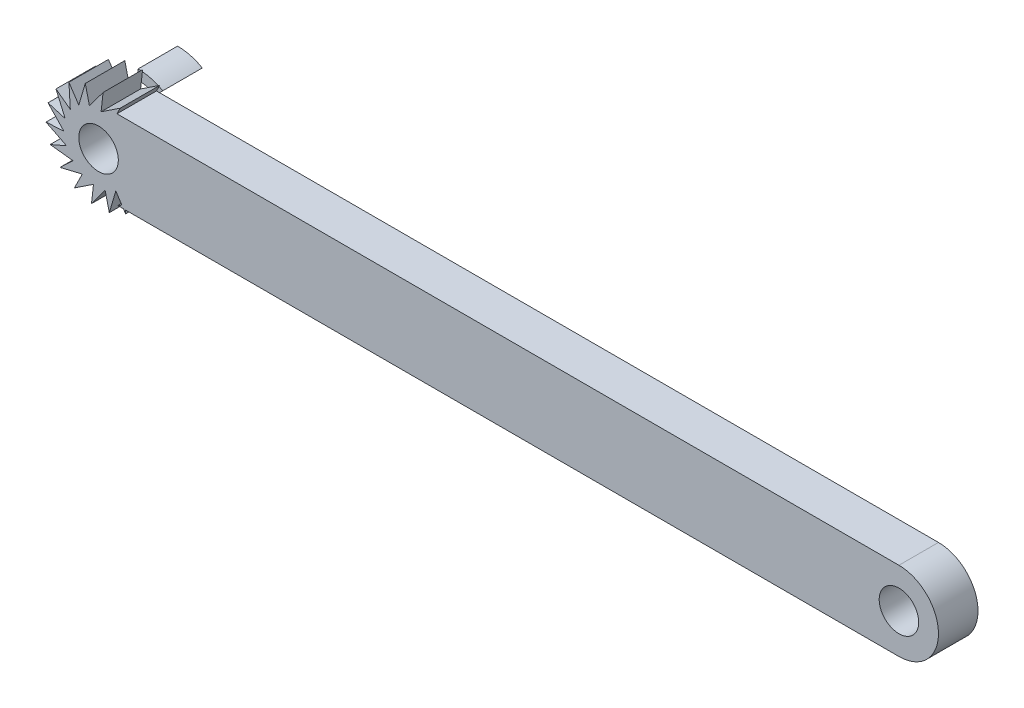
SolidWorks part; units mm, degrees
material "1060 Alloy"
ref_plane "Front Plane" through (0, 0, 0) normal (0, 0, 1) x (1, 0, 0)
ref_plane "Top Plane" through (0, 0, 0) normal (0, 1, 0) x (1, 0, 0)
ref_plane "Right Plane" through (0, 0, 0) normal (1, 0, 0) x (0, 0, -1)
sketch "Sketch1" plane through (0, 0, 0) normal (0, 0, 1) x (1, 0, 0)
  line L0 (-71.3706, 0) -> (333.6294, 0) construction
  line L1 (-71.3706, 20) -> (333.6294, 20)
  line L2 (-71.3706, -20) -> (333.6294, -20)
  arc A0 (-71.3706, 20) -> (-71.3706, -20) centre (-71.3706, 0) ccw
  arc A1 (333.6294, -20) -> (333.6294, 20) centre (333.6294, 0) ccw
  circle A2 centre (-71.3706, 0) radius 10
  circle A3 centre (333.6294, 0) radius 10
  point P3 (131.1294, 0)
extrude "Boss-Extrude1" add sketch "Sketch1" along normal blind 20
sketch "Sketch2" plane through (0, 0, 0) normal (0, 0, -1) x (-1, 0, 0)
  line L0 (71.3706, -20) -> (71.3706, -25)
  line L1 (62.5643, -17.9569) -> (58.8706, -21.6506)
  arc A0 (62.5643, -17.9569) -> (71.3706, -20) centre (71.3706, 0) ccw
  arc A1 (58.8706, -21.6506) -> (71.3706, -25) centre (71.3706, 0) ccw
  arc A2 (71.3706, -20) -> (71.3706, 20) centre (71.3706, 0) ccw construction
  dimension "D1" = 50
  dimension "D2" = 45
extrude "Boss-Extrude2" add sketch "Sketch2" along normal blind 20
ref_plane "Plane1" through (0, 0, 15) normal (0, 0, 1) x (1, 0, 0)
sketch "Sketch5" plane through (0, 0, 15) normal (0, 0, 1) x (1, 0, 0)
  circle A0 centre (-72.0022, 0) radius 20
  arc A1 (-71.3706, 20) -> (-71.3706, -20) centre (-71.3706, 0) ccw construction
  circle A2 centre (-72.0022, 0) radius 13.4404
extrude "Boss-Extrude3" add sketch "Sketch5" along normal blind 5 contours A0
mirror "Mirror1" about plane through (0, 0, 0) normal (0, 1, 0) of "Boss-Extrude2"
sketch "Sketch7" plane through (0, 0, -20) normal (0, 0, -1) x (-1, 0, 0)
  line L4 (62.5643, -17.9569) -> (58.8706, -21.6506)
  line L5 (71.3706, -25) -> (71.3706, -20)
  line L6 (62.5643, -17.9569) -> (58.8706, -21.6506)
  line L7 (71.3706, -25) -> (71.3706, -20)
  arc A4 (62.5643, -17.9569) -> (71.3706, -20) centre (71.3706, 0) ccw
  arc A5 (58.8706, -21.6506) -> (71.3706, -25) centre (71.3706, 0) ccw
  arc A6 (62.5643, -17.9569) -> (71.3706, -20) centre (71.3706, 0) ccw
  arc A7 (58.8706, -21.6506) -> (71.3706, -25) centre (71.3706, 0) ccw
  dimension "D1" = 0
extrude "Cut-Extrude2" cut sketch "Sketch7" against normal blind 20
sketch "Sketch8" plane through (0, 0, 20) normal (0, 0, 1) x (1, 0, 0)
  line L0 (-85.6463, 10.091) -> (-86.3578, 21.6776)
  line L1 (-85.6463, 10.091) -> (-92.9062, 15.4604)
  line L2 (-81.3721, 14.149) -> (-86.3578, 21.6776)
  line L3 (-88.2748, 4.8159) -> (-92.9062, 15.4604)
  line L4 (-81.3721, 14.149) -> (-78.0779, 25.2802)
  line L5 (-75.9678, 16.5004) -> (-78.0779, 25.2802)
  line L6 (-75.9678, 16.5004) -> (-69.0651, 25.8336)
  line L7 (-70.0852, 16.8617) -> (-69.0651, 25.8336)
  line L8 (-70.0852, 16.8617) -> (-60.4067, 23.2711)
  line L9 (-64.4338, 15.1891) -> (-60.4067, 23.2711)
  line L10 (-64.4338, 15.1891) -> (-53.1468, 17.9018)
  line L11 (-59.6952, 11.6845) -> (-53.1468, 17.9018)
  line L12 (-59.6952, 11.6845) -> (-48.1611, 10.3732)
  line L13 (-56.4411, 6.7706) -> (-48.1611, 10.3732)
  line L14 (-56.4411, 6.7706) -> (-46.0511, 1.5935)
  line L15 (-55.0638, 1.0401) -> (-46.0511, 1.5935)
  line L16 (-55.0638, 1.0401) -> (-47.0711, -7.3784)
  line L17 (-55.7296, -4.8159) -> (-47.0711, -7.3784)
  line L18 (-55.7296, -4.8159) -> (-51.0982, -15.4604)
  line L19 (-58.3581, -10.091) -> (-51.0982, -15.4604)
  line L20 (-58.3581, -10.091) -> (-57.6466, -21.6776)
  line L21 (-62.6323, -14.149) -> (-57.6466, -21.6776)
  line L22 (-62.6323, -14.149) -> (-65.9265, -25.2802)
  line L23 (-68.0366, -16.5004) -> (-65.9265, -25.2802)
  line L24 (-68.0366, -16.5004) -> (-74.9393, -25.8336)
  line L25 (-73.9192, -16.8617) -> (-74.9393, -25.8336)
  line L26 (-73.9192, -16.8617) -> (-83.5977, -23.2711)
  line L27 (-79.5707, -15.1891) -> (-83.5977, -23.2711)
  line L28 (-79.5707, -15.1891) -> (-90.8576, -17.9018)
  line L29 (-84.3092, -11.6845) -> (-90.8576, -17.9018)
  line L30 (-84.3092, -11.6845) -> (-95.8433, -10.3732)
  line L31 (-87.5634, -6.7706) -> (-95.8433, -10.3732)
  line L32 (-87.5634, -6.7706) -> (-97.9533, -1.5935)
  line L33 (-88.9406, -1.0401) -> (-97.9533, -1.5935)
  line L34 (-88.9406, -1.0401) -> (-96.9333, 7.3784)
  line L35 (-88.2748, 4.8159) -> (-96.9333, 7.3784)
  circle A0 centre (-72.0022, 0) radius 26 construction
  circle A1 centre (-72.0022, 0) radius 16.9703 construction
  point P61 (-72.0022, 0)
  dimension "D1" = 18
extrude "Boss-Extrude4" add sketch "Sketch8" against normal blind 20
sketch "Sketch10" plane through (0, 0, 20) normal (0, 0, 1) x (1, 0, 0)
  line L36 (-90.8576, -17.9018) -> (-79.5707, -15.1891)
  line L37 (-84.3092, -11.6845) -> (-90.8576, -17.9018)
  line L38 (-95.8433, -10.3732) -> (-84.3092, -11.6845)
  line L39 (-87.5634, -6.7706) -> (-95.8433, -10.3732)
  line L40 (-97.9533, -1.5935) -> (-87.5634, -6.7706)
  line L41 (-88.9406, -1.0401) -> (-97.9533, -1.5935)
  line L42 (-96.9333, 7.3784) -> (-88.9406, -1.0401)
  line L43 (-88.2748, 4.8159) -> (-96.9333, 7.3784)
  line L44 (-92.9062, 15.4604) -> (-88.2748, 4.8159)
  line L45 (-85.6463, 10.091) -> (-92.9062, 15.4604)
  line L46 (-86.3578, 21.6776) -> (-85.6463, 10.091)
  line L47 (-81.3721, 14.149) -> (-86.3578, 21.6776)
  line L48 (-78.0779, 25.2802) -> (-81.3721, 14.149)
  line L49 (-75.9678, 16.5004) -> (-78.0779, 25.2802)
  line L50 (-69.0651, 25.8336) -> (-75.9678, 16.5004)
  line L51 (-70.0852, 16.8617) -> (-69.0651, 25.8336)
  line L52 (-60.4067, 23.2711) -> (-70.0852, 16.8617)
  line L53 (-64.4338, 15.1891) -> (-60.4067, 23.2711)
  line L54 (-53.1468, 17.9018) -> (-64.4338, 15.1891)
  line L55 (-59.6952, 11.6845) -> (-53.1468, 17.9018)
  line L56 (-48.1611, 10.3732) -> (-59.6952, 11.6845)
  line L57 (-56.4411, 6.7706) -> (-48.1611, 10.3732)
  line L58 (-46.0511, 1.5935) -> (-56.4411, 6.7706)
  line L59 (-55.0638, 1.0401) -> (-46.0511, 1.5935)
  line L60 (-47.0711, -7.3784) -> (-55.0638, 1.0401)
  line L61 (-55.7296, -4.8159) -> (-47.0711, -7.3784)
  line L62 (-51.0982, -15.4604) -> (-55.7296, -4.8159)
  line L63 (-58.3581, -10.091) -> (-51.0982, -15.4604)
  line L64 (-57.6466, -21.6776) -> (-58.3581, -10.091)
  line L65 (-62.6323, -14.149) -> (-57.6466, -21.6776)
  line L66 (-65.9265, -25.2802) -> (-62.6323, -14.149)
  line L67 (-68.0366, -16.5004) -> (-65.9265, -25.2802)
  line L68 (-74.9393, -25.8336) -> (-68.0366, -16.5004)
  line L69 (-73.9192, -16.8617) -> (-74.9393, -25.8336)
  line L70 (-83.5977, -23.2711) -> (-73.9192, -16.8617)
  line L71 (-79.5707, -15.1891) -> (-83.5977, -23.2711)
  line L72 (-86.6815, -16.8981) -> (-79.5707, -15.1891)
  line L73 (-84.3092, -11.6845) -> (-88.2294, -15.4064)
  line L74 (-91.5474, -10.8616) -> (-84.3092, -11.6845)
  line L75 (-87.5634, -6.7706) -> (-92.5024, -8.9196)
  line L76 (-94.0745, -3.5262) -> (-87.5634, -6.7706)
  line L77 (-88.9406, -1.0401) -> (-94.313, -1.37)
  line L78 (-93.956, 4.2425) -> (-88.9406, -1.0401)
  line L79 (-88.2748, 4.8159) -> (-93.4477, 6.3468)
  line L80 (-91.1923, 11.5212) -> (-88.2748, 4.8159)
  line L81 (-85.6463, 10.091) -> (-90.005, 13.3147)
  line L82 (-86.0972, 17.4331) -> (-85.6463, 10.091)
  line L83 (-81.3721, 14.149) -> (-84.3864, 18.7007)
  line L84 (-79.2695, 21.2538) -> (-81.3721, 14.149)
  line L85 (-75.9678, 16.5004) -> (-77.254, 21.852)
  line L86 (-71.5281, 22.5034) -> (-75.9678, 16.5004)
  line L87 (-70.0852, 16.8617) -> (-69.4582, 22.3763)
  line L88 (-63.8154, 21.0137) -> (-70.0852, 16.8617)
  line L101 (-62.6323, -14.149) -> (-59.5564, -18.7937)
  line L102 (-64.7511, -21.3085) -> (-62.6323, -14.149)
  line L103 (-68.0366, -16.5004) -> (-66.7453, -21.8734)
  line L104 (-72.4427, -22.458) -> (-68.0366, -16.5004)
  line L105 (-73.9192, -16.8617) -> (-74.5383, -22.3064)
  line L106 (-80.0529, -20.9236) -> (-73.9192, -16.8617)
  line L107 (-79.5707, -15.1891) -> (-81.9959, -20.0564)
  arc A0 (-51.2654, 9.0226) -> (-52.1518, 10.8269) centre (-71.8704, 0.0204) ccw
  arc A1 (-71.5281, 22.5034) -> (-77.254, 21.852) centre (-71.8704, 0.0204) ccw
  arc A2 (-63.8154, 21.0137) -> (-69.4582, 22.3763) centre (-71.8704, 0.0204) ccw
  arc A3 (-79.2695, 21.2538) -> (-84.3864, 18.7007) centre (-71.8704, 0.0204) ccw
  arc A4 (-86.0972, 17.4331) -> (-90.005, 13.3147) centre (-71.8704, 0.0204) ccw
  arc A5 (-91.1923, 11.5212) -> (-93.4477, 6.3468) centre (-71.8704, 0.0204) ccw
  arc A6 (-93.956, 4.2425) -> (-94.313, -1.37) centre (-71.8704, 0.0204) ccw
  arc A7 (-94.0745, -3.5262) -> (-92.5024, -8.9196) centre (-71.8704, 0.0204) ccw
  arc A8 (-91.5474, -10.8616) -> (-88.2294, -15.4064) centre (-71.8704, 0.0204) ccw
  arc A9 (-86.6815, -16.8981) -> (-81.9959, -20.0564) centre (-71.8704, 0.0204) ccw
  arc A10 (-80.0529, -20.9236) -> (-74.5383, -22.3064) centre (-71.8704, 0.0204) ccw
  arc A11 (-72.4427, -22.458) -> (-66.7453, -21.8734) centre (-71.8704, 0.0204) ccw
  arc A12 (-64.7511, -21.3085) -> (-59.5564, -18.7937) centre (-71.8704, 0.0204) ccw
  dimension "D1" = 0
extrude "Cut-Extrude9" cut sketch "Sketch10" against normal blind 20 contours L103 A11 L104 | L106 L105 A10 | L72 L107 A9 | L74 L73 A8 | L76 L75 A7 | L78 L77 A6 | L80 L79 A5 | L82 L81 A4 | L84 L83 A3 | L86 L85 A1 | L88 L87 A2 | L101 A12 L102
ref_axis "Axis2" through (-71.3706, 0, -20) along (0, 0, 1)
sketch "Sketch13" plane through (0, 0, 0) normal (0, 0, -1) x (-1, 0, 0)
  circle A3 centre (71.3706, 0) radius 10
  circle A4 centre (71.3706, 0) radius 10
  dimension "D2" = 0
extrude "Cut-Extrude10" cut sketch "Sketch13" against normal blind 20
ref_plane "Plane2" through (40, 0, 0) normal (1, 0, 0) x (0, 0, -1)
sketch "Sketch16" plane through (0, 0, 20) normal (0, 0, 1) x (1, 0, 0)
  circle A0 centre (-36.7494, 0) radius 8.1386
sketch "Sketch18" plane through (0, 0, 0) normal (0, 0, -1) x (-1, 0, 0)
  line L1 (-88.105, 70.239) -> (-127.8309, 70.239)
  line L2 (-88.105, 70.239) -> (-88.105, -80.3132)
  line L3 (-88.105, -80.3132) -> (-127.8309, -80.3132)
  line L4 (-127.8309, 70.239) -> (-127.8309, -80.3132)
